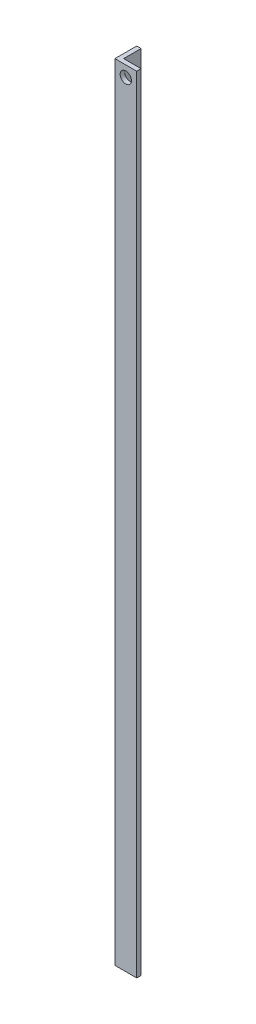
SolidWorks part; units mm, degrees
ref_plane "Front Plane" through (0, 0, 0) normal (0, 0, 1) x (1, 0, 0)
ref_plane "Top Plane" through (0, 0, 0) normal (0, 1, 0) x (1, 0, 0)
ref_plane "Right Plane" through (0, 0, 0) normal (1, 0, 0) x (0, 0, -1)
sketch "Sketch1" plane through (0, 0, 0) normal (0, 1, 0) x (1, 0, 0)
  line L0 (0, 0) -> (0, 10)
  line L1 (0, 10) -> (2, 10)
  line L2 (2, 10) -> (2, 2)
  line L3 (2, 2) -> (10, 2)
  line L4 (10, 2) -> (10, 0)
  line L5 (10, 0) -> (0, 0)
  dimension "D1" = 10
  dimension "D2" = 2
extrude "Boss-Extrude1" add sketch "Sketch1" along normal blind 360
hole_wizard "#6 (0.204) Diameter Hole2" positions "Sketch6" profile "Sketch7" hole size "#6" standard "ANSI Inch" end condition through all
sketch "Sketch6" plane through (0, 0, 0) normal (-1, 0, 0) x (0, 0, 1)
  line L0 (0, 360) -> (0, 0) construction
  line L1 (-10, 0) -> (0, 0) construction
  point P0 (-5, 5)
  dimension "D1" = 5
  dimension "D2" = 5
sketch "Sketch7" plane through (0, 5, -5) normal (0, 1, 0) x (0, 0, 1)
  line L0 (0, 0) -> (0, 10)
  line L1 (0, 10) -> (2.5908, 10)
  line L2 (2.5908, 10) -> (2.5908, 0)
  line L5 (2.5908, 0) -> (0, 0)
  line L11 (0, -6.35) -> (0, 107.95) construction
  dimension "Thru Hole Dia." = 5.1816
  dimension "Thru Hole Depth" = 10
hole_wizard "#6 (0.204) Diameter Hole3" positions "Sketch8" profile "Sketch9" hole size "#6" standard "ANSI Inch" end condition through all
sketch "Sketch8" plane through (0, 0, 0) normal (0, 0, 1) x (1, 0, 0)
  line L0 (0, 360) -> (0, 0) construction
  line L1 (0, 360) -> (10, 360) construction
  point P0 (5, 355)
  dimension "D1" = 5
  dimension "D2" = 5
sketch "Sketch9" plane through (5, 355, 0) normal (1, 0, 0) x (0, -1, 0)
  line L0 (0, 0) -> (0, 10)
  line L1 (0, 10) -> (2.5908, 10)
  line L2 (2.5908, 10) -> (2.5908, 0)
  line L5 (2.5908, 0) -> (0, 0)
  line L11 (0, -6.35) -> (0, 107.95) construction
  dimension "Thru Hole Dia." = 5.1816
  dimension "Thru Hole Depth" = 10
